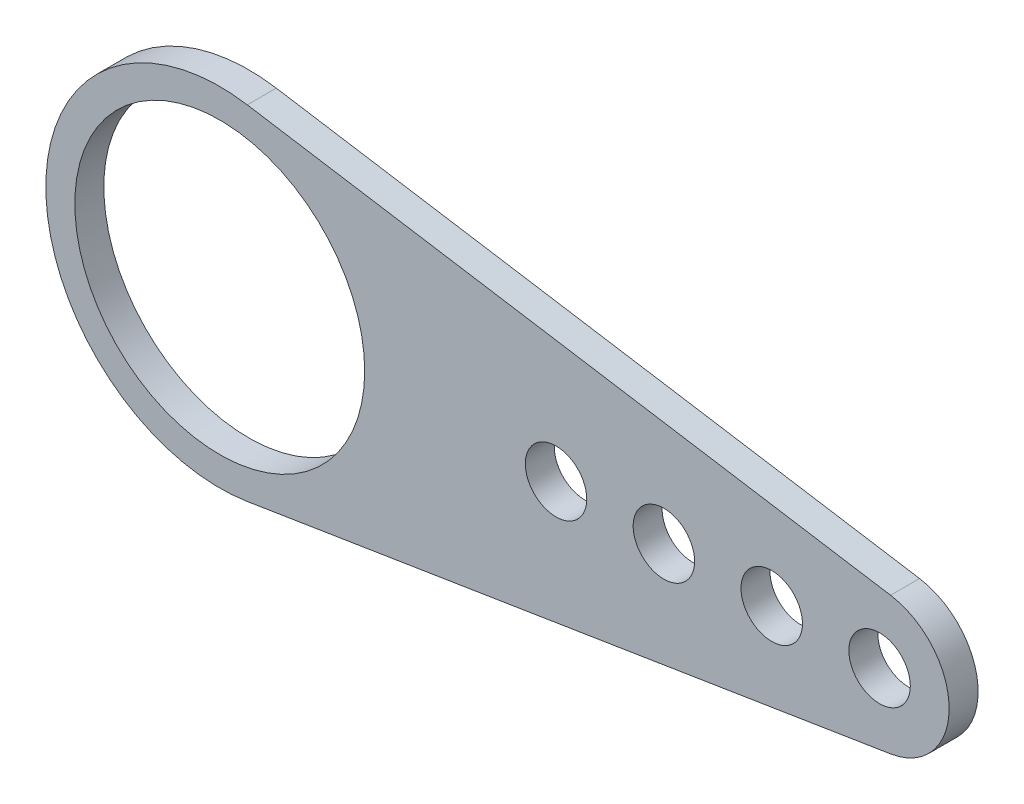
SolidWorks part; units mm, degrees
material "AISI 4340 Steel, normalized"
ref_plane "X-Y Datum" through (0, 0, 0) normal (0, 0, 1) x (1, 0, 0)
ref_plane "X-Z Datum" through (0, 0, 0) normal (0, 1, 0) x (1, 0, 0)
ref_plane "Y-Z Datum" through (0, 0, 0) normal (1, 0, 0) x (0, 0, -1)
sketch "Flat sketch" plane through (0, 0, 0) normal (0, 0, 1) x (1, 0, 0)
  line L0 (-15.875, 0) -> (72.263, 0) construction
  line L2 (3.0132, 18.8102) -> (73.4683, 7.5241)
  line L3 (3.0132, -18.8102) -> (73.4683, -7.5241)
  line L4 (73.4683, 7.5241) -> (73.4683, -7.5241) construction
  circle A0 centre (0, 0) radius 15.875
  circle A1 centre (0, 0) radius 19.05
  circle A2 centre (72.263, 0) radius 3.3655
  circle A8 centre (72.263, 0) radius 7.62
  circle A9 centre (60.452, 0) radius 3.3655
  circle A10 centre (48.641, 0) radius 3.3655
  circle A11 centre (36.83, 0) radius 3.3655
  point P5 (15.875, 0)
  point P9 (19.05, 0)
  point P10 (-19.05, 0)
  point P16 (79.883, 0)
  dimension "D1" = 31.75
  dimension "D2" = 38.1
  dimension "D3" = 6.731
  dimension "D7" = 15.24
  dimension "D5" = 17.78
  dimension "D6" = 11.811
  dimension "D8" = 98.933
  dimension "D4" = 4
extrude "Extrude face" add sketch "Flat sketch" along normal blind 3.175 contours A1 A0 | A8 A2 | A11 | A10 | A9 | A2 | A8 L2 A1 L3 A11 A10 A9 region at (38.1144, 12.3785, 0) region at (14.0866, 12.0097, 0) region at (77.8976, 4.8039, 0) region at (72.263, 0, 0) region at (60.452, 0, 0) region at (48.641, 0, 0) region at (36.83, 0, 0)
extrude "Extrude cut - holes" cut sketch "Flat sketch<4>" along normal up to surface (3.175 mm away) contours A11 | A10 | A9 | A2 region at (72.263, 0, 0) region at (60.452, 0, 0) region at (48.641, 0, 0) region at (36.83, 0, 0) up to face at (15.875, 0, 3.175)
sketch "Flat sketch<4>" plane through (0, 0, 0) normal (0, 0, 1) x (1, 0, 0) same geometry as "Flat sketch"
equation "\"Torsion Bar O.D.\"= 1.25"
equation "\"Lever I.D. Torsion O.D. Clearance\"= 0"
equation "\"Lever I.D.\"= \"Torsion Bar O.D.\" + \"Lever I.D. Torsion O.D. Clearance\""
equation "\"D1@Flat sketch\" = \"Lever I.D.\""
equation "\"Lever O.D.\"= 1.5"
equation "\"D2@Flat sketch\" = \"Lever O.D.\""
equation "\"Lever Rod end I.D.\"= 0.265"
equation "\"D3@Flat sketch\" = \"Lever Rod end I.D.\""
equation "\"Distance b/w Lever Rod end holes\"= 0"
equation "\"Number of Lever Rod end holes\"= 0"
equation "\"Lever arc radius\"= 0.5"
equation "\"Lever rod end hole and Lever O.D. clearance\"= 0.7"
equation "\"Lever thickness\"= 1 / 8in"
equation "\"D1@Extrude face\" = \"Lever thickness\""
equation "\"D5@Flat sketch\"=\"Lever rod end hole and Lever O.D. clearance\""
